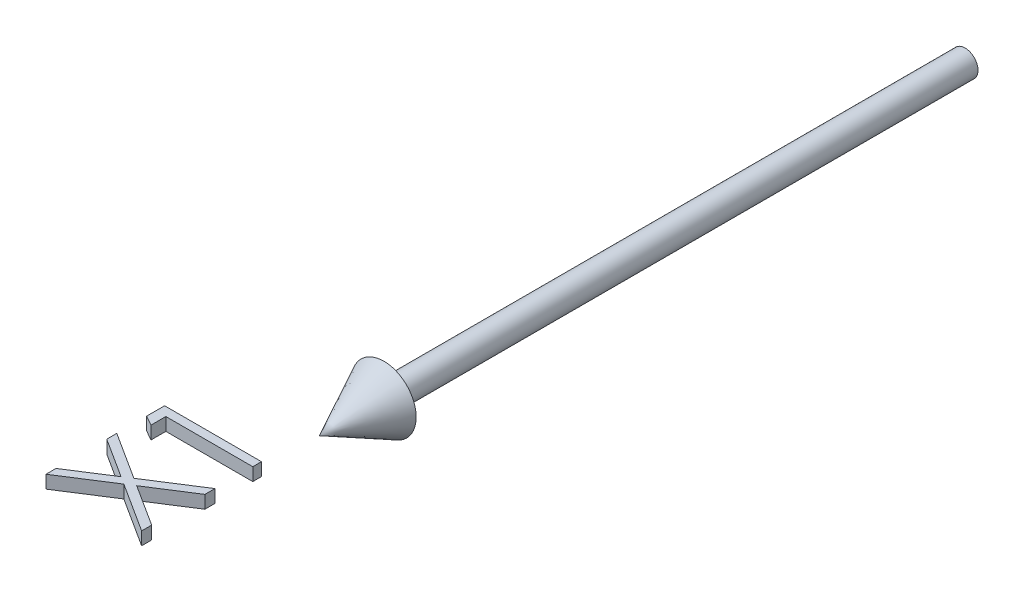
SolidWorks part; units mm, degrees
ref_plane "Front Plane" through (0, 0, 0) normal (0, 0, 1) x (1, 0, 0)
ref_plane "Top Plane" through (0, 0, 0) normal (0, 1, 0) x (1, 0, 0)
ref_plane "Right Plane" through (0, 0, 0) normal (1, 0, 0) x (0, 0, -1)
sketch "Sketch2" plane through (0, 0, 0) normal (0, 1, 0) x (1, 0, 0)
  line L0 (0, 41.95) -> (0, -114.4521) construction
  line L1 (-36.8894, 0) -> (41.4965, 0) construction
  line L2 (0, -100) -> (5, -90)
  line L3 (5, -90) -> (2, -90)
  line L4 (2, -90) -> (2, 0)
  line L5 (2, 0) -> (0, 0)
  line L6 (0, 0) -> (0, -100)
  dimension "D1" = 100
  dimension "D2" = 2
  dimension "D3" = 10
  dimension "D4" = 5
revolve "Revolve1" add sketch "Sketch2" angle 360 about L0
sketch "Sketch3" plane through (0, 0, 0) normal (0, 1, 0) x (1, 0, 0)
  line L0 (0, -103.9528) -> (0, -147.2622) construction
  line L1 (-18.6107, -118.3811) -> (18.3141, -118.3811) construction
  text T0 "X1" font "Century Gothic" height 15
extrude "Boss-Extrude1" add sketch "Sketch3" against normal blind 1 and the other way blind 1 separate body
equation "\"frame_arrow_length\"=100"
equation "\"D1@Sketch2\"=\"frame_arrow_length\""
equation "\"frame_arrow_odA\"=4"
equation "\"D2@Sketch2\"=\"frame_arrow_odA\"/2"
equation "\"frame_arrow_head_od\"=5"
equation "\"D4@Sketch2\"=\"frame_arrow_head_od\""
equation "\"frame_arrow_head_length\"=10"
equation "\"D3@Sketch2\"=\"frame_arrow_head_length\""
equation "\"tvarobot_theta1\"=30"
equation "\"link0_ringA_odA\"= 40"
equation "\"link0_ringA_odB\"= 25"
equation "\"link0_ringA_id\"= 20"
equation "\"link0_ringA_thickness\"= (\"link0_ringA_odB\" - \"link0_ringA_id\")/2"
equation "\"link0_ringA_height\"= 3"
equation "\"link0_ringA_heightA\"= 1.5"
equation "\"link0_ringA_heightB\"=\"link0_ringA_height\"-\"link0_ringA_heightA\""
equation "\"link0_ringB_odA\"= 40"
equation "\"link0_ringB_odB\"= 29"
equation "\"link0_ringB_id\"= \"link0_shaftA_bearing_id\"+1"
equation "\"link0_ringB_thickness\"= (\"link0_ringB_odB\" - \"link0_ringB_id\")/2"
equation "\"link0_ringB_height\"= 3"
equation "\"link0_ringB_heightA\"= 1.5"
equation "\"link0_ringB_heightB\"=\"link0_ringB_height\"-\"link0_ringB_heightA\""
equation "\"link0_shaftA_bearing_od\"=27"
equation "\"link0_shaftA_bearing_id\"=20"
equation "\"link0_shaftA_thrust_bearing_od\"=35"
equation "\"link0_shaftA_thrust_bearing_id\"=20.04"
equation "\"link0_shaftA_retaining_ring_id\"=18.5"
equation "\"link0_shaftA_retaining_ring_groove_width\"=1.5"
equation "\"link0_shaftA_spline_length\"=8.0"
equation "\"link0_shaftA_spline_depth\"=1.0"
equation "\"link0_shaftA_spline_width\"=4.0"
equation "\"link0_shaftA_odA\"=\"link0_shaftA_bearing_id\""
equation "\"link0_shaftA_odB\"=35"
equation "\"link0_shaftA_odC\"=\"link0_shaftA_bearing_id\""
equation "\"link0_shaftA_odD\"=\"link0_shaftA_odC\"-2*\"link0_shaftA_spline_depth\""
equation "\"link0_shaftA_odE\"=\"link0_shaftA_bearing_id\""
equation "\"link0_shaftA_odF\"=\"link0_shaftA_odE\"-2*\"link0_shaftA_spline_depth\""
equation "\"link0_shaftA_idA\"=10"
equation "\"link0_shaftA_idB\"=6"
equation "\"link0_shaftA_length\"=39.5"
equation "\"link0_shaftA_lengthA\"=8.0"
equation "\"link0_shaftA_lengthB\"=12.0"
equation "\"link0_shaftA_lengthC\"=35.0"
equation "\"link0_shaftA_lengthD\"=39.0"
equation "\"link0_shaftA_lengthE\"=\"link0_shaftA_length\"-\"link0_shaftA_lengthD\""
equation "\"link0_shaftA_offsetX\"=11"
equation "\"link0_shaftA_offsetY\"=0"
equation "\"link0_shaftA_bolt_pattern_dia\"=14"
equation "\"link0_motor_center_dist\"=26"
equation "\"link0_46t_pulley_spline_length\"=8"
equation "\"link0_46t_pulley_spline_depth\"=\"link0_shaftA_spline_depth\"*1.025"
equation "\"link0_46t_pulley_spline_width\"=\"link0_shaftA_spline_width\"*1.05"
equation "\"link0_46t_pulley_idA\"=\"link0_shaftA_bearing_id\"*1.025"
equation "\"link0_46t_pulley_idB\"=\"link0_46t_pulley_idA\"-2*\"link0_46t_pulley_spline_depth\""
equation "\"link0_shaftB_spline_length\"=10"
equation "\"link0_shaftB_spline_depth\"=1.0"
equation "\"link0_shaftB_spline_width\"=1.25"
equation "\"link0_shaftB_length\"=7"
equation "\"link0_shaftB_lengthA\"=1.5"
equation "\"link0_shaftB_lengthB\"=2.75"
equation "\"link0_shaftB_odA\"=32"
equation "\"link0_shaftB_odB\"=22"
equation "\"link0_shaftB_odC\"=20"
equation "\"link0_shaftB_idA\"=10"
equation "\"link0_shaftB_bolt_diameter\"=19"
equation "\"link0_shaftB_bearing_od\"=27"
equation "\"link0_shaftB_bearing_id\"=20"
equation "\"link0_motor_length\"=46.5"
equation "\"link0_motor_width\"=28.5"
equation "\"link0_motor_height\"=34"
equation "\"link0_motor_offset\"=8"
equation "\"link0_shellA_thickness\"=2.5"
equation "\"link0_shellB_thickness\"=\"link0_shellA_thickness\""
equation "\"link0_plateA_shellA_height\"=48"
equation "\"link0_shellA_width\" =\"link0_plateA_width\""
equation "\"link0_shellA_height\" = \"link0_plateA_shellA_height\"-\"link0_plateA_height\""
equation "\"link0_shellA_length\" = \"link0_plateA_lengthB\" "
equation "\"link0_shellB_length\"=\"link0_shellA_length\""
equation "\"link0_shellA_radius\" = 0.375*25.4"
equation "\"link0_shellA_radiusA\"= \"link0_plateA_radiusA\""
equation "\"link0_shellA_radiusB\"= \"link0_plateA_radiusB\""
equation "\"link0_shellA_radiusC\"= 3"
equation "\"link0_postA_height\"=7"
equation "\"link0_postA_width\"=16"
equation "\"link0_postA_length\"=20"
equation "\"link0_postA_posX\"=22"
equation "\"link0_postA_posY\"=17.5"
equation "\"link0_postA_pocket_width\"=6.0"
equation "\"link0_postA_pocket_length\"=2.5"
equation "\"link0_postA_pocket_depth\"=9"
equation "\"link0_postA_pocket_posZ\"=10"
equation "\"link0_postB_height\"=7"
equation "\"link0_postB_width\"=16"
equation "\"link0_postB_length\"=20"
equation "\"link0_postB_posX\"=22"
equation "\"link0_postB_posY\"=17.5"
equation "\"link0_postB_id\"=3.0"
equation "\"link0_postB_pocket_width\"=6.0"
equation "\"link0_postB_pocket_length\"=2.5"
equation "\"link0_postB_pocket_depth\"=9"
equation "\"link0_postB_pocket_posZ\"=10"
equation "\"link0_postC_height\"=7"
equation "\"link0_postC_width\"=16"
equation "\"link0_postC_length\"=20"
equation "\"link0_postC_posX\"=22"
equation "\"link0_postC_posY\"=17.5"
equation "\"link0_postC_id\"=3.0"
equation "\"link0_postC_pocket_width\"=6.0"
equation "\"link0_postC_pocket_length\"=2.5"
equation "\"link0_postC_pocket_depth\"=9"
equation "\"link0_postC_pocket_posZ\"=10"
equation "\"link0_postD_height\"=7"
equation "\"link0_postD_width\"=16"
equation "\"link0_postD_length\"=20"
equation "\"link0_postD_posX\"=22"
equation "\"link0_postD_posY\"=17.5"
equation "\"link0_postD_id\"=3.0"
equation "\"link0_postD_pocket_width\"=6.0"
equation "\"link0_postD_pocket_length\"=3.0"
equation "\"link0_postD_pocket_depth\"=9"
equation "\"link0_postD_pocket_posZ\"=10"
equation "\"link0_postE_height\"=5"
equation "\"link0_postE_width\"=16"
equation "\"link0_postE_length\"=\"link0_plateE_lengthA\"-\"link0_lip_height\""
equation "\"link0_postE_posZ\"=22"
equation "\"link0_postE_posX\"=17.5"
equation "\"link0_postE_posY\"=22"
equation "\"link0_postE_id\"=3.0"
equation "\"link0_postE_cbore_id\"=6.5"
equation "\"link0_postE_hole_id\"=3"
equation "\"link0_postF_posZ\"=22"
equation "\"link0_postF_posX\"=17.5"
equation "\"link0_postF_posY\"=\"link0_plateB_lengthA\"+4"
equation "\"link0_postF_id\"=3.0"
equation "\"link0_postF_cbore_id\"=6.5"
equation "\"link0_postF_hole_id\"=3"
equation "\"link0_postG_posZ\"=22"
equation "\"link0_postG_posX\"=17.5"
equation "\"link0_postG_posY\"=\"link0_plateB_lengthA\"+12"
equation "\"link0_postG_id\"=3.0"
equation "\"link0_postG_cbore_id\"=6.5"
equation "\"link0_postG_hole_id\"=3"
equation "\"link0_postHIJ_posY\"=6"
equation "\"link0_postH_posX\"=28"
equation "\"link0_postH_posY\"=20"
equation "\"link0_postH_posZ\"=20"
equation "\"link0_postH_length\"=10"
equation "\"link0_postI_posX\"=28"
equation "\"link0_postI_posY\"=20"
equation "\"link0_postI_posZ\"=135"
equation "\"link0_postI_length\"=10"
equation "\"link0_postJ_posX\"=28"
equation "\"link0_postJ_posY\"=20"
equation "\"link0_postJ_posZ\"=175"
equation "\"link0_postJ_length\"=10"
equation "\"link0_postK_posX\"=28"
equation "\"link0_postK_posY\"=20"
equation "\"link0_postK_posZ\"=175"
equation "\"link0_postK_length\"=10"
equation "\"link0_postL_posX\"=28"
equation "\"link0_postL_posY\"=20"
equation "\"link0_postL_posZ\"=135"
equation "\"link0_postL_length\"=10"
equation "\"link0_postM_posX\"=28"
equation "\"link0_postM_posY\"=20"
equation "\"link0_postM_posZ\"=35"
equation "\"link0_postM_length\"=10"
equation "\"link0_plateA_lengthA\"=30"
equation "\"link0_plateA_lengthB\"=150"
equation "\"link0_plateA_lengthC\"=30"
equation "\"link0_plateA_length\"=\"link0_plateA_lengthA\"+\"link0_plateA_lengthB\"+\"link0_plateA_lengthC\""
equation "\"link0_plateA_width\"=  68"
equation "\"link0_plateA_height\"= \"link0_plateA_radiusA\""
equation "\"link0_plateA_thickness\"=\"link0_shellA_thickness\""
equation "\"link0_plateA_radius\"= 9.5"
equation "\"link0_plateA_radiusA\"= 18"
equation "\"link0_plateA_radiusB\"= 18"
equation "\"link0_plateA_radiusC\"= 3"
equation "\"link0_plateB_length\"= 40"
equation "\"link0_plateB_width\"= \"link0_plateA_width\"*1.005"
equation "\"link0_plateB_height\"= \"link0_plateA_shellA_height\"*1.005"
equation "\"link0_plateB_lengthA\"=\"link0_lip_height\"+\"link0_plateD_thickness\"+\"link0_motor_mount_thickness\""
equation "\"link0_plateB_lengthB\"=\"link0_plateB_height\"-\"link0_plateB_lengthA\""
equation "\"link0_plateB_radiusA\"= \"link0_plateA_radiusA\""
equation "\"link0_plateB_radiusB\"= \"link0_plateA_radiusB\""
equation "\"link0_plateB_radiusC\"= 3"
equation "\"link0_plateB_idA\"=\"link0_shaftA_odC\"+1"
equation "\"link0_plateB_idB\"=\"link0_shaftA_bearing_od\"-2"
equation "\"link0_plateB_idC\"=\"link0_shaftA_bearing_od\"*1.005"
equation "\"link0_plateB_idD\"=\"link0_shaftA_thrust_bearing_od\"+1 "
equation "\"link0_plateB_depthA\"=1.0"
equation "\"link0_plateB_depthB\"=2.0"
equation "\"link0_plateB_depthC\"=8"
equation "\"link0_plateB_depthD\"=\"link0_plateB_length\"-\"link0_lip_height\"-\"link0_plateD_thickness\" "
equation "\"link0_plateC_length\"=\"link0_plateB_length\""
equation "\"link0_plateC_width\"= \"link0_plateB_width\""
equation "\"link0_plateC_height\"= .1*25.4"
equation "\"link0_plateA_hole_od\" = 0.1*25.4"
equation "\"link0_plateA_hole_delx\" = 0.5*25.4"
equation "\"link0_plateA_hole_delz\" = 0.75*25.4"
equation "\"link0_plateA_hole_offx\" = 0.0*25.4"
equation "\"link0_plateA_hole_offz\" = \"link0_plateA_length\"/2"
equation "\"link0_plateB_hole_od\" = 0.1*25.4"
equation "\"link0_plateB_hole_delx\"= 0.75*25.4"
equation "\"link0_plateB_hole_delz\"= 0.75*25.4"
equation "\"link0_plateB_hole_offx\"= 0.0*25.4"
equation "\"link0_plateB_hole_offz\"= 0.0*25.4"
equation "\"link0_plateC_hole_od\"= 0.1*25.4"
equation "\"link0_plateC_hole_delx\"= 0.75*25.4"
equation "\"link0_plateC_hole_delz\"= 0.75*25.4"
equation "\"link0_plateC_hole_offx\"= 0.0*25.4"
equation "\"link0_plateC_hole_offz\"= 0.0*25.4"
equation "\"link0_plateD_height\"=\"link0_plateB_height\"-2*\"link0_shellA_thickness\""
equation "\"link0_plateD_width\"=\"link0_plateB_width\"-2*\"link0_shellA_thickness\""
equation "\"link0_plateD_thickness\"=10"
equation "\"link0_plateD_radiusA\"=\"link0_plateB_radiusA\"-\"link0_shellA_thickness\""
equation "\"link0_plateD_odA\"= .375*25.4"
equation "\"link0_plateD_odB\"= .375*25.4"
equation "\"link0_plateD_bearing_id\"=20"
equation "\"link0_plateD_bearing_od\"=27"
equation "\"link0_plateE_radiusA\"=\"link0_plateA_radiusA\""
equation "\"link0_plateE_radiusB\"=\"link0_plateA_radiusB\""
equation "\"link0_plateE_radiusC\"=8.0"
equation "\"link0_plateE_length\"=30"
equation "\"link0_plateE_lengthA\"=16"
equation "\"link0_plateE_height\"=\"link0_plateB_height\""
equation "\"link0_plateE_width\"=\"link0_plateB_width\""
equation "\"link0_plateE_odA\"=\"gantry_coupler_id\"*0.99"
equation "\"link0_plateE_idA\"=\"link0_plateE_odA\"-20.0"
equation "\"link0_plateE_spline_depth\"=\"link0_poleA_spline_depth\"*1.05"
equation "\"link0_plateE_spline_width\"=\"link0_poleA_spline_width\"*1.075"
equation "\"link0_plateE_spline_length\"=\"link0_poleA_spline_length\""
equation "\"link0_plateE_coupler_length\"=46"
equation "\"link0_lip_height\"=5.0"
equation "\"link0_lip_thickness\"=2.0"
equation "\"link0_motor_mount_thickness\"=8.0"
equation "\"link0_motor_mount_idA\"=22"
equation "\"link0_motor_mount_idB\"=\"link0_shaftB_bearing_od\"*1.005"
equation "\"link0_motor_mount_idC\"=\"link0_shaftB_bearing_od\"-2"
equation "\"link0_motor_mount_depthA\"=5.5"
equation "\"link0_motor_mount_height\"=\"link0_plateD_height\""
equation "\"link0_motor_mount_width\"=\"link0_plateD_width\""
equation "\"link0_motor_mountL_height\"=36"
equation "\"link0_motor_mountL_heightA\"=12"
equation "\"link0_motor_mountL_length\"=50"
equation "\"link0_motor_mountL_lengthA\"=36"
equation "\"gantry_coupler_od\"=25.4*2.0"
equation "\"gantry_coupler_id\"=1.645*25.4"
equation "\"gantry_coupler_offsetX\"=\"link0_plateE_width\"/2"
equation "\"link0_poleA_odA\"=20"
equation "\"link0_poleA_odB\"=36"
equation "\"link0_poleA_idA\"=\"link0_poleA_odA\"-2*\"link0_poleA_thickness\""
equation "\"link0_poleA_idB\"=(\"link0_plateE_idA\"/2+1.5*\"link0_lip_thickness\")*1.04"
equation "\"link0_poleA_thickness\"=3.5"
equation "\"link0_poleA_length\"=100"
equation "\"link0_poleA_lengthA\"=18.5"
equation "\"link0_poleA_lengthB\"=80"
equation "\"link0_poleA_gasket_thickness\"=1.5"
equation "\"link0_poleA_spline_depth\"=1.0"
equation "\"link0_poleA_spline_width\"=4.0"
equation "\"link0_poleA_spline_length\"=10.0"
equation "\"link1_plateB_length\"=30"
equation "\"link1_lip_height\"=\"link0_lip_height\""
equation "\"link0_tension_plateA_width\"=12"
equation "\"link0_tension_plateA_lengthA\"=10.5"
equation "\"link0_tension_plateB_width\"=\"link0_tension_plateA_width\""
equation "\"link0_tension_plateB_lengthA\"=\"link0_tension_plateA_lengthA\""
equation "\"link0_tension_wheelA_posZ\"=7"
equation "\"link0_tension_wheelA_posX\"=\"link0_plateD_height\"/2-\"link0_tension_plateA_lengthA\""
equation "\"link0_m2_clear_hole_id\"=2.35"
equation "\"link0_m2_insert_hole_id\"=2.5"
equation "\"link0_m2_tap_hole_id\"=1.75"
equation "\"link0_m2_nut_socket_width\"=4.25"
equation "\"link0_m2_nut_socket_depth\"=2.5"
equation "\"link0_m2_cbore_id\"=3.75"
equation "\"link0_m2_cbore_depth\"=7"
equation "\"link0_m2_5_clear_hole_id\"=2.75"
equation "\"link0_m2_5_insert_hole_id\"=2.75"
equation "\"link0_m2_5_tap_hole_id\"=2.25"
equation "\"link0_m2_5_nut_socket_width\"=5.25"
equation "\"link0_m2_5_nut_socket_depth\"=2.5"
equation "\"link0_m2_5_cbore_id\"=4.75"
equation "\"link0_m2_5_cbore_depth\"=2.5"
equation "\"link0_m2_5_insert_access_length\"=6.0"
equation "\"link0_m2_5_insert_access_width\"=3.0"
equation "\"link0_m3_clear_hole_id\"=3.25"
equation "\"link0_m3_insert_hole_id\"=3"
equation "\"link0_m3_tap_hole_id\"=2.75"
equation "\"link0_m3_nut_socket_width\"=5.75"
equation "\"link0_m3_nut_socket_depth\"=4.0"
equation "\"link0_m3_cbore_id\"=5.75"
equation "\"link0_m3_cbore_depth\"=3.5"
equation "\"link0_m3_insert_access_length\"=4.5"
equation "\"link0_m3_insert_access_width\"=3.5"
equation "\"link0_rpi_mount_height\"=6"
equation "\"link0_rpi_mount_width\"=49"
equation "\"link0_rpi_mount_length\"=58"
equation "\"link0_rpi_mount_post_od\"=6"
equation "\"link0_rpi_mount_posZ\"=72"
equation "\"link0_rpi_mount_posX\"=11.5"
equation "\"link0_mcu_mount_height\"=5"
equation "\"link0_mcu_mount_width\"=49"
equation "\"link0_mcu_mount_length\"=58"
equation "\"link0_mcu_mount_post_od\"=6"
equation "\"link0_mcu_mount_posZ\"=164"
equation "\"link0_mcu_mount_posX\"=4"
equation "\"link0_pwr_mount_height\"=4"
equation "\"link0_pwr_mount_width\"=15.75"
equation "\"link0_pwr_mount_length\"=75.75"
equation "\"link0_pwr_mount_post_od\"=6"
equation "\"link0_pwr_mount_posZ\"=75"
equation "\"link0_pwr_mount_posX\"=16"
equation "\"link0_pwr_board_height\"=6"
equation "\"link0_pwr_board_width\"=21"
equation "\"link0_pwr_board_length\"=80"
